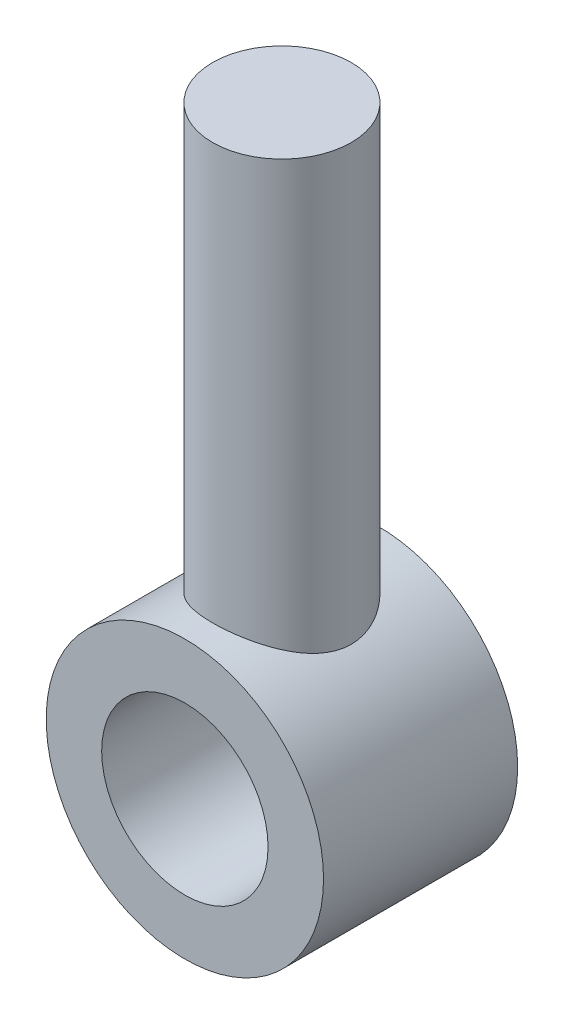
SolidWorks part; units mm, degrees
note: '?' marks a value the reader was unsure of.
ref_plane "Front Plane" through (0, 0, 0) normal (0, 0, 1) x (1, 0, 0)
ref_plane "Top Plane" through (0, 0, 0) normal (0, 1, 0) x (1, 0, 0)
ref_plane "Right Plane" through (0, 0, 0) normal (1, 0, 0) x (0, 0, -1)
sketch "Sketch1" plane through (0, 0, 0) normal (0, 0, 1) x (1, 0, 0)
  circle A0 centre (0, 0) radius 5
  circle A1 centre (0, 0) radius 3
  dimension "D1" = 10
  dimension "D2" = 6
extrude "Boss-Extrude1" add sketch "Sketch1" along normal blind 7
sketch "Sketch3" plane through (0, 0, 0) normal (0, 1, 0) x (1, 0, 0)
  line L1 (5, -7) -> (5, 0) construction
  circle A1 centre (0, -3.5) radius 2.5
  dimension "D1" = 3.5
  dimension "D2" = 5
  dimension "D3" = 5
extrude "Boss-Extrude2" add sketch "Sketch3" along normal blind 17 from offset 3
cosmetic thread "Cosmetic Thread2" parameters "D1"=10, "D2"=4.11
thread "Thread1" [suppressed] pitch 1.0583 start angle 0, offset 2, length 13, pitch 1.0583, diameter 5
ref_plane "Plane1" through (-2.5, 22, 3.5) normal (0, 0, 1) x (-1, 0, 0)
sketch "Thread Profile1" plane through (-2.5, 22, 3.5) normal (0, 0, 1) x (-1, 0, 0)
  line L0 (0, 0) -> (0, 1.0583) construction
  line L11 (0, 0) -> (0, 0.926)
  line L12 (0, 0.926) -> (-0.5728, 0.5953)
  line L13 (-0.5728, 0.5953) -> (-0.5728, 0.3307)
  line L15 (-0.5728, 0.3307) -> (0, 0)
  line L17 (-0.5728, 0.463) -> (0, 0.463) construction
  point P2 (0, 0)
  dimension "Pitch" = 1.0583
  dimension "Profile_Angle" = 60
  dimension "Profile_Land" = 0.2646
  dimension "Profile_Height" = 0.5728
ref_axis "Axis1" through (0, 20, 3.5) along (0, -1, 0)?
